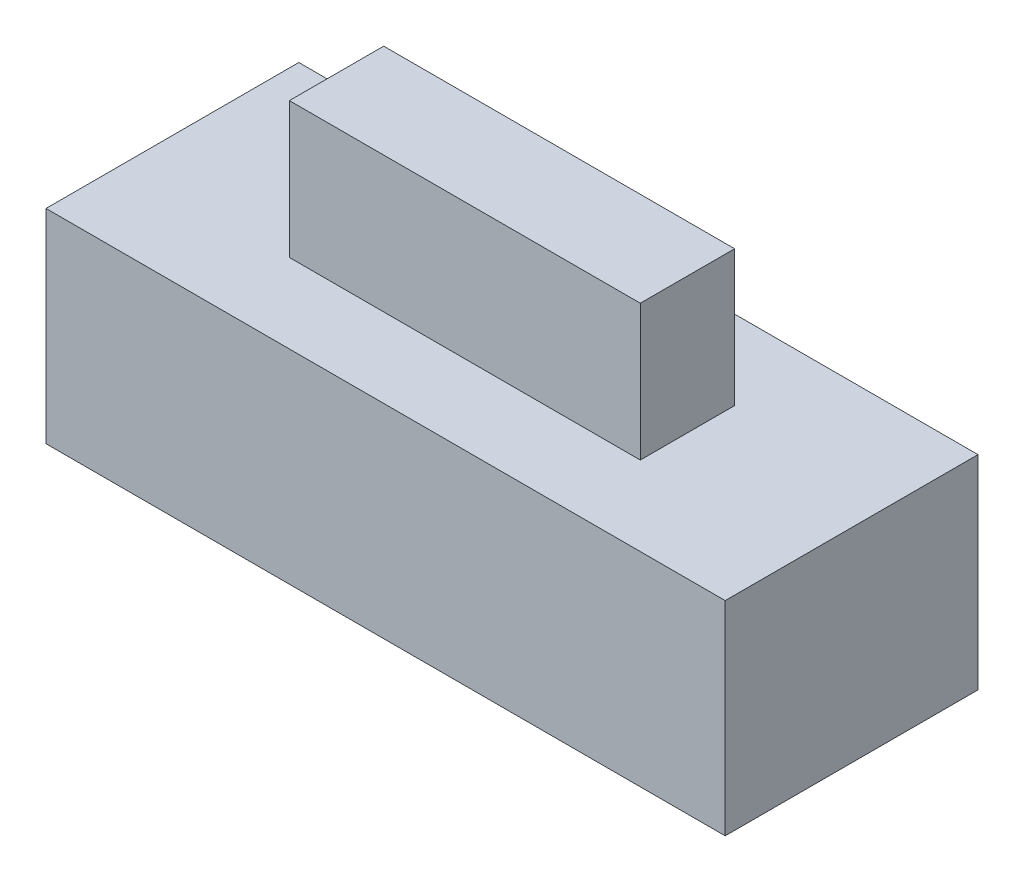
SolidWorks part; units mm, degrees
ref_plane "Front Plane" through (0, 0, 0) normal (0, 0, 1) x (1, 0, 0)
ref_plane "Top Plane" through (0, 0, 0) normal (0, 1, 0) x (1, 0, 0)
ref_plane "Right Plane" through (0, 0, 0) normal (1, 0, 0) x (0, 0, -1)
sketch "Sketch1" plane through (0, 0, 0) normal (0, 1, 0) x (1, 0, 0)
  line L0 (-42, 0) -> (42, 0) construction
  line L1 (-42, -13.75) -> (42, -13.75)
  line L2 (-42, -13.75) -> (-42, 13.75)
  line L3 (-42, 13.75) -> (42, 13.75)
  line L4 (42, -13.75) -> (42, 13.75)
  line L5 (-42, -13.75) -> (42, 13.75) construction
  line L6 (-42, 13.75) -> (42, -13.75) construction
  line L8 (10, -5) -> (15.5, -5)
  line L9 (10, -5) -> (10, 5)
  line L10 (10, 5) -> (15.5, 5)
  line L11 (15.5, -5) -> (15.5, 5)
  line L12 (10, -5) -> (15.5, 5) construction
  line L13 (10, 5) -> (15.5, -5) construction
  line L25 (1.5, -5) -> (1.5, 5)
  line L32 (1.5, -5) -> (7, -5)
  line L33 (7, -5) -> (7, 5)
  line L34 (1.5, 5) -> (7, 5)
  line L39 (-7, -5) -> (-7, 5)
  line L40 (-7, -5) -> (-1.5, -5)
  line L41 (-1.5, -5) -> (-1.5, 5)
  line L42 (-7, 5) -> (-1.5, 5)
  line L47 (-15.5, -5) -> (-15.5, 5)
  line L48 (-15.5, -5) -> (-10, -5)
  line L49 (-10, -5) -> (-10, 5)
  line L50 (-15.5, 5) -> (-10, 5)
  line L55 (1.5, 3.3547) -> (-1.5, 3.3547) construction
  point P0 (0, 0)
  point P5 (12.75, 0)
  point P9 (0, 0)
  point P46 (0, 3.3547)
  dimension "D2" = 84
  dimension "D3" = 27.5
  dimension "D4" = 10
  dimension "D5" = 5.5
  dimension "D6" = 4
  dimension "D7" = 8.5
  dimension "D8" = 8.75
  dimension "D9" = 31
extrude "Boss-Extrude1" add sketch "Sketch1" along normal blind 5 contours L50 L49 L48 L47 L3 L2 L1 L4 L10 L11 L8 L9 L34 L33 L32 L25 L42 L41 L40 L39 region at (0, 0, 0)
sketch "Sketch2" plane through (0, 5, 0) normal (0, 1, 0) x (1, 0, 0)
  line L0 (10, -5) -> (15.5, 5) construction
  line L1 (12.75, 13.75) -> (12.75, -13.75) construction
  line L2 (-42, -13.75) -> (42, -13.75) construction
  line L3 (1.5, -5) -> (7, 5) construction
  line L4 (11.25, -3.25) -> (14.25, -3.25)
  line L5 (11.25, -3.25) -> (11.25, 3.25)
  line L6 (11.25, 3.25) -> (14.25, 3.25)
  line L7 (14.25, -3.25) -> (14.25, 3.25)
  line L8 (11.25, -3.25) -> (14.25, 3.25) construction
  line L9 (11.25, 3.25) -> (14.25, -3.25) construction
  line L10 (4.25, 13.75) -> (4.25, -13.75) construction
  line L11 (2.75, -3.25) -> (2.75, 3.25)
  line L12 (2.75, -3.25) -> (5.75, -3.25)
  line L13 (5.75, -3.25) -> (5.75, 3.25)
  line L14 (2.75, 3.25) -> (5.75, 3.25)
  line L15 (-5.75, -3.25) -> (-5.75, 3.25)
  line L16 (-5.75, -3.25) -> (-2.75, -3.25)
  line L17 (-2.75, -3.25) -> (-2.75, 3.25)
  line L18 (-5.75, 3.25) -> (-2.75, 3.25)
  line L19 (-14.25, -3.25) -> (-14.25, 3.25)
  line L20 (-14.25, -3.25) -> (-11.25, -3.25)
  line L21 (-11.25, -3.25) -> (-11.25, 3.25)
  line L22 (-14.25, 3.25) -> (-11.25, 3.25)
  line L24 (-42, -13.75) -> (42, -13.75)
  line L25 (-42, -13.75) -> (-42, 13.75)
  line L26 (-42, 13.75) -> (42, 13.75)
  line L27 (42, -13.75) -> (42, 13.75)
  line L28 (-42, -13.75) -> (42, 13.75) construction
  line L29 (-42, 13.75) -> (42, -13.75) construction
  point P4 (12.75, 0)
  point P9 (12.75, 0)
  point P18 (4.25, 3.25)
  point P21 (4.25, 0)
  point P22 (0, 0)
  dimension "D1" = 3
  dimension "D2" = 6.5
  dimension "D3" = 4
extrude "Boss-Extrude2" add sketch "Sketch2" along normal blind 3
sketch "Sketch5" plane through (0, 8, 0) normal (0, 1, 0) x (1, 0, 0)
  line L0 (11.25, 3.25) -> (14.25, -3.25) construction
  line L1 (12.75, 13.75) -> (12.75, -13.75) construction
  line L2 (9.75, 6.25) -> (15.75, 6.25)
  line L3 (9.75, 6.25) -> (9.75, -3.25)
  line L4 (9.75, -3.25) -> (15.75, -3.25)
  line L5 (15.75, 6.25) -> (15.75, -3.25)
  line L6 (9.75, 6.25) -> (15.75, -3.25) construction
  line L7 (9.75, -3.25) -> (15.75, 6.25) construction
  line L8 (-42, -13.75) -> (42, -13.75) construction
  line L9 (11.25, -3.25) -> (14.25, -3.25) construction
  line L10 (2.75, 3.25) -> (5.75, -3.25) construction
  line L24 (16.05, -2.25) -> (16.95, -2.25)
  line L25 (14.55, -0.75) -> (14.55, 0.75)
  line L26 (16.05, 2.25) -> (16.95, 2.25)
  line L27 (16.95, -2.25) -> (16.95, 2.25)
  line L28 (14.55, -2.25) -> (16.95, 2.25) construction
  line L29 (14.55, 2.25) -> (16.95, -2.25) construction
  line L32 (10.95, -0.75) -> (10.95, 0.75)
  line L36 (2.45, -0.75) -> (2.45, 0.75)
  line L37 (1.25, 6.25) -> (1.25, -3.25)
  line L38 (1.25, 6.25) -> (7.25, 6.25)
  line L39 (7.25, 6.25) -> (7.25, -3.25)
  line L40 (1.25, -3.25) -> (7.25, -3.25)
  line L41 (6.05, -0.75) -> (6.05, 0.75)
  line L48 (-6.05, -0.75) -> (-6.05, 0.75)
  line L49 (-7.25, 6.25) -> (-7.25, -3.25)
  line L50 (-7.25, 6.25) -> (-1.25, 6.25)
  line L51 (-1.25, 6.25) -> (-1.25, -3.25)
  line L52 (-7.25, -3.25) -> (-1.25, -3.25)
  line L53 (-2.45, -0.75) -> (-2.45, 0.75)
  line L60 (-14.55, -0.75) -> (-14.55, 0.75)
  line L61 (-15.75, 6.25) -> (-15.75, -3.25)
  line L62 (-15.75, 6.25) -> (-9.75, 6.25)
  line L63 (-9.75, 6.25) -> (-9.75, -3.25)
  line L64 (-15.75, -3.25) -> (-9.75, -3.25)
  line L65 (-10.95, -0.75) -> (-10.95, 0.75)
  line L69 (42, 13.75) -> (-42, 13.75) construction
  line L90 (-9.45, 2.25) -> (-8.55, 2.25) [skipped]
  line L91 (-8.5, -2.25) -> (-7.5, -2.25) [skipped]
  line L92 (-8.55, -2.25) -> (-8.55, 2.25) [skipped]
  line L95 (-1, 2.25) -> (-0.5, 2.25) [skipped]
  line L97 (-1, -2.25) -> (-0.5, -2.25) [skipped]
  line L99 (-0.05, -2.25) -> (-0.05, 2.25) [skipped]
  line L101 (7, -2.25) -> (7.5, -2.25) [skipped]
  line L102 (7, 2.25) -> (7.5, 2.25) [skipped]
  line L103 (8.45, -2.25) -> (8.45, 2.25) [skipped]
  line L116 (-15.75, 6.25) -> (15.75, 6.25)
  line L122 (-15.75, -3.25) -> (15.75, -3.25)
  line L123 (-15.75, -3.25) -> (-15.75, -6.25)
  line L124 (-15.75, -6.25) -> (15.75, -6.25)
  line L125 (15.75, -3.25) -> (15.75, -6.25)
  line L126 (15.75, 6.25) -> (23.25, 6.25)
  line L127 (15.75, 6.25) -> (15.75, -6.25)
  line L128 (15.75, -6.25) -> (23.25, -6.25)
  line L129 (23.25, 6.25) -> (23.25, -6.25)
  line L130 (-15.75, 6.25) -> (-23.25, 6.25)
  line L131 (-15.75, 6.25) -> (-15.75, -6.25)
  line L132 (-15.75, -6.25) -> (-23.25, -6.25)
  line L133 (-23.25, 6.25) -> (-23.25, -6.25)
  arc A0 (16.05, -2.25) -> (14.55, -0.75) centre (16.05, -0.75) cw
  arc A1 (14.55, 0.75) -> (16.05, 2.25) centre (16.05, 0.75) cw
  arc A2 (9.45, -2.25) -> (10.95, -0.75) centre (9.45, -0.75) ccw
  arc A3 (10.95, 0.75) -> (9.45, 2.25) centre (9.45, 0.75) ccw
  arc A4 (0.95, -2.25) -> (2.45, -0.75) centre (0.95, -0.75) ccw
  arc A5 (2.45, 0.75) -> (0.95, 2.25) centre (0.95, 0.75) ccw
  arc A6 (6.05, 0.75) -> (7.55, 2.25) centre (7.55, 0.75) cw
  arc A7 (7.55, -2.25) -> (6.05, -0.75) centre (7.55, -0.75) cw
  arc A8 (-7.55, -2.25) -> (-6.05, -0.75) centre (-7.55, -0.75) ccw
  arc A9 (-6.05, 0.75) -> (-7.55, 2.25) centre (-7.55, 0.75) ccw
  arc A10 (-2.45, 0.75) -> (-0.95, 2.25) centre (-0.95, 0.75) cw
  arc A11 (-0.95, -2.25) -> (-2.45, -0.75) centre (-0.95, -0.75) cw
  arc A12 (-16.05, -2.25) -> (-14.55, -0.75) centre (-16.05, -0.75) ccw
  arc A13 (-14.55, 0.75) -> (-16.05, 2.25) centre (-16.05, 0.75) ccw
  arc A14 (-10.95, 0.75) -> (-9.45, 2.25) centre (-9.45, 0.75) cw
  arc A15 (-9.45, -2.25) -> (-10.95, -0.75) centre (-9.45, -0.75) cw
  point P4 (12.75, 1.5)
  point P9 (15.75, 0)
  point P10 (4.25, 0)
  point P15 (12.75, 0)
  point P26 (4.25, 6.25)
  point P41 (0, 0)
  point P87 (4.25, -3.25)
  line M10 (-5.75, -3.25) -> (-5.75, 3.25)
  line M12 (-2.75, 3.25) -> (-2.75, -3.25)
  line M13 (-2.75, -3.25) -> (-5.75, -3.25)
  line M14 (2.75, -3.25) -> (2.75, 3.25)
  line M16 (5.75, 3.25) -> (5.75, -3.25)
  line M17 (5.75, -3.25) -> (2.75, -3.25)
  line M18 (14.25, 3.25) -> (14.25, -3.25)
  line M19 (14.25, -3.25) -> (11.25, -3.25)
  line M20 (11.25, -3.25) -> (11.25, 3.25)
  line M22 (-14.25, -3.25) -> (-14.25, 3.25)
  line M24 (-11.25, 3.25) -> (-11.25, -3.25)
  line M25 (-11.25, -3.25) -> (-14.25, -3.25)
  dimension "D5" = 1.5
  dimension "D1" = 9.5
  dimension "D2" = 6
  dimension "D3" = 1.2
  dimension "D4" = 1
  dimension "D7" = 2.5
  dimension "D8" = 46.5
  dimension "D9" = 7.5
  dimension "D10" = 7.5
  dimension "D11" = 3
  dimension "D6" = 4
extrude "Boss-Extrude4" add sketch "Sketch5" along normal blind 15 contours L130 L133 L132 L123 L131 L61 | L125 L4 L122 L40 L52 L64 L123 L124 M19 M17 M13 M25 | L63 L122 L49 L116 | L51 L122 L37 L116 | L39 L122 L3 L116 | L5 A1 L26 L27 L24 A0 L127 L125 L128 L129 L126 | A1 L127 A0 L24 L27 L26 region at (8.5, 8, -1.5) region at (19.6923, 8, 0) region at (16.3506, 8, 0) region at (0, 8, -1.5) region at (0, 8, 4.75) region at (-8.5, 8, -1.5) region at (-19.5, 8, 0)
extrude "Boss-Extrude5" add sketch "Sketch5<5>" along normal blind 5 from offset 2 contours A13 L131 A12 M22 | A15 L63 A14 M24 | A9 L49 A8 M10 | A11 L51 A10 M12 | A5 L37 A4 M14 | A7 L39 A6 M16 | A3 L3 A2 M20 | A1 A0 L5 M18 region at (10.2915, 8, 0) region at (15.2085, 8, 0) region at (1.7915, 8, 0) region at (6.7085, 8, 0) region at (-1.7915, 8, 0) region at (-6.7085, 8, 0) region at (-10.2915, 8, 0) region at (-15.2085, 8, 0)
sketch "Sketch5<5>" plane through (0, 8, 0) normal (0, 1, 0) x (1, 0, 0) same geometry as "Sketch5"
sketch "Sketch7" plane through (0, 0, -6.25) normal (0, 0, -1) x (-1, 0, 0)
  line L0 (-23.25, 23) -> (23.25, 23)
extrude "Extrude-Thin2" add sketch "Sketch7" against normal up to surface (12.5 mm away) thin up to face at (0, 15.5, 6.25) thin type one direction reverse wall 3
sketch "Sketch9" plane through (0, 0, -6.25) normal (0, 0, -1) x (-1, 0, 0)
  line L0 (15.75, 8) -> (23.25, 26) construction
  line L1 (0, 0) -> (0, 26) construction
  line L2 (-23.25, 26) -> (23.25, 26) construction
  circle A0 centre (19.5, 17) radius 1.25
  circle A1 centre (-19.5, 17) radius 1.25
  dimension "D1" = 2.5
extrude "Cut-Extrude2" cut sketch "Sketch9" against normal blind 10
chamfer "Chamfer1" distance 0.5 angle 60 16 edges at (4.25, 5, -3.25) (5.75, 5, 0) (4.25, 5, 3.25) (2.75, 5, 0) (-4.25, 5, -3.25) (-2.75, 5, 0) (-4.25, 5, 3.25) (-5.75, 5, 0) (-12.75, 5, -3.25) (-11.25, 5, 0) (-12.75, 5, 3.25) (-14.25, 5, 0) (14.25, 5, 0) (12.75, 5, -3.25) (12.75, 5, 3.25) (11.25, 5, 0) first distance on face at (4.25, 5, 0) first distance on face at (-4.25, 5, 0) first distance on face at (-12.75, 5, 0) first distance on face at (12.75, 5, 0)
chamfer "Chamfer2" distance 1 angle 80 16 edges at (15.5, 0, 0) (12.75, 0, -5) (12.75, 0, 5) (10, 0, 0) (7, 0, 0) (4.25, 0, 5) (1.5, 0, 0) (4.25, 0, -5) (-4.25, 0, -5) (-1.5, 0, 0) (-4.25, 0, 5) (-7, 0, 0) (-10, 0, 0) (-12.75, 0, -5) (-12.75, 0, 5) (-15.5, 0, 0) first distance on face at (12.75, 0, 0)
extrude "Extrude-Thin1" add sketch "Sketch1<5>" along normal up to surface (8 mm away) and the other way blind 19 thin contours L3 L4 L1 L2 up to face at (0, 8, 0) thin type one direction wall 3
sketch "Sketch1<5>" plane through (0, 0, 0) normal (0, 1, 0) x (1, 0, 0) same geometry as "Sketch1"
